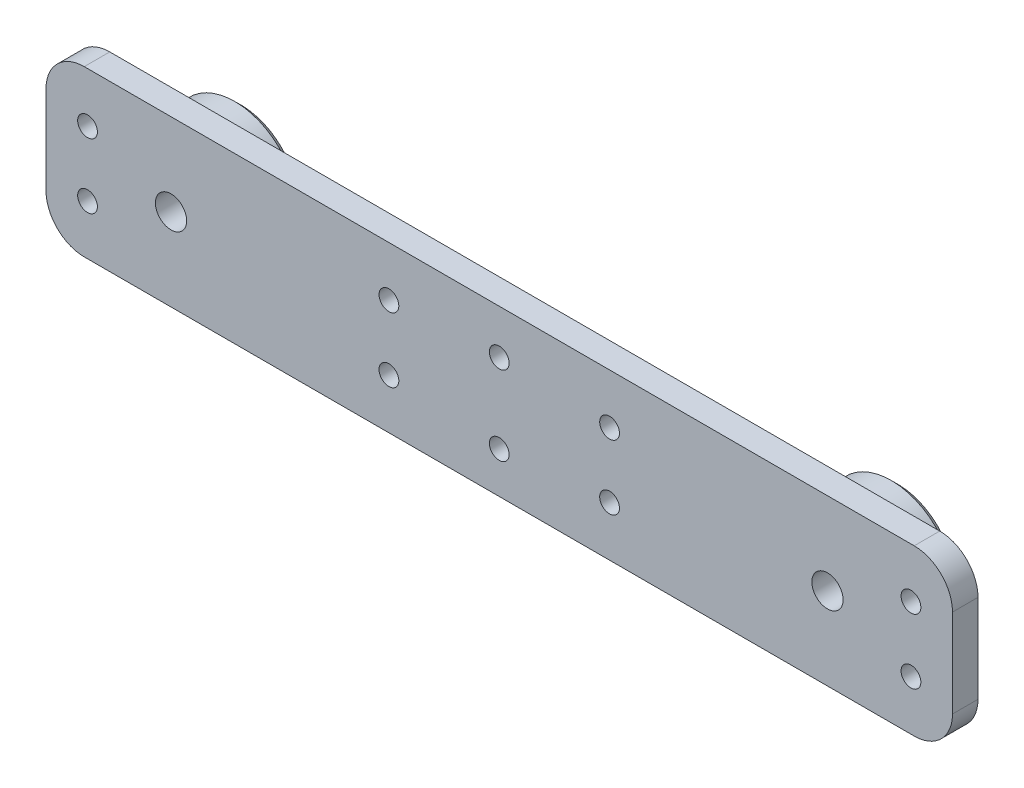
SolidWorks part; units mm, degrees
material "PET"
ref_plane "Front Plane" through (0, 0, 0) normal (0, 0, 1) x (1, 0, 0)
ref_plane "Top Plane" through (0, 0, 0) normal (0, 1, 0) x (1, 0, 0)
ref_plane "Right Plane" through (0, 0, 0) normal (1, 0, 0) x (0, 0, -1)
ref_plane "Plane1" through (0, 0, -8.279) normal (0, 0, -1) x (-1, 0, 0)
sketch "Sketch1" plane through (0, 0, -8.279) normal (0, 0, -1) x (-1, 0, 0)
  line L0 (-112, 9.158) -> (30.1427, 9.158)
  line L1 (30.1427, 9.158) -> (30.1427, 35)
  line L2 (30.1427, 35) -> (-112, 35)
  line L3 (-112, 35) -> (-112, 9.158)
extrude "Boss-Extrude1" add sketch "Sketch1" against normal blind 4
ref_plane "Plane2" through (0, 22.079, 0) normal (0, 1, 0) x (1, 0, 0)
sketch "Sketch2" plane through (0, 22.079, 0) normal (0, 1, 0) x (1, 0, 0)
  line L0 (-0.54, 15.279) -> (-10.54, 15.279)
  line L1 (-10.54, 15.279) -> (-10.54, 8.279)
  line L2 (-10.54, 8.279) -> (-0.54, 8.279)
  line L3 (-0.54, 8.279) -> (-0.54, 15.279)
  line L4 (-10.54, 15.279) -> (-10.54, 8.279) construction
revolve "Revolve1" add sketch "Sketch2" angle 360 about L4 reverse direction yes
sketch "Sketch3" plane through (0, 22.079, 0) normal (0, 1, 0) x (1, 0, 0)
  line L0 (102.397, 15.279) -> (92.397, 15.279)
  line L1 (92.397, 15.279) -> (92.397, 8.279)
  line L2 (92.397, 8.279) -> (102.397, 8.279)
  line L3 (102.397, 8.279) -> (102.397, 15.279)
  line L4 (92.397, 15.279) -> (92.397, 8.279) construction
revolve "Revolve2" add sketch "Sketch3" angle 360 about L4 reverse direction yes
hole_wizard "Ø3.1 (3.1) Diameter Hole1" positions "Sketch5" profile "Sketch4" hole size "Ø3.1" standard "ANSI Metric"
sketch "Sketch5" plane through (0, 0, -4.279) normal (0, 0, 1) x (1, 0, 0)
  point P0 (40.9286, 28.0395)
  point P1 (40.9286, 15.6185)
  point P2 (58.2273, 27.164)
  point P3 (23.63, 27.164)
  point P4 (-23.63, 27.164)
  point P5 (-23.63, 16.994)
  point P6 (23.63, 16.994)
  point P7 (58.2273, 16.994)
  point P8 (105.4873, 27.164)
  point P9 (105.4873, 16.994)
sketch "Sketch4" plane through (40.9286, 28.0395, -4.279) normal (1, 0, 0) x (0, -1, 0)
  line L0 (0, 0) -> (0, 11)
  line L1 (0, 11) -> (1.55, 11)
  line L2 (1.55, 11) -> (1.55, 0)
  line L5 (1.55, 0) -> (0, 0)
  line L11 (0, -6.35) -> (0, 107.95) construction
  dimension "Thru Hole Dia." = 3.1
  dimension "Thru Hole Depth" = 11
hole_wizard "Ø6.0 (6) Diameter Hole1" positions "Sketch7" profile "Sketch6" hole size "Ø6.0" standard "ANSI Metric"
sketch "Sketch7" plane through (0, 0, -15.279) normal (0, 0, -1) x (-1, 0, 0)
  point P0 (-92.397, 22.0793)
  point P1 (10.54, 22.079)
sketch "Sketch6" plane through (92.397, 22.0793, -15.279) normal (1, 0, 0) x (0, 1, 0)
  line L0 (0, 0) -> (0, 11)
  line L1 (0, 11) -> (3, 11)
  line L2 (3, 11) -> (3, 0)
  line L5 (3, 0) -> (0, 0)
  line L11 (0, -6.35) -> (0, 107.95) construction
  dimension "Thru Hole Dia." = 6
  dimension "Thru Hole Depth" = 11
chamfer "Chamfer1" distance 1 angle 45 4 edges at (92.397, 32.079, -8.279) (-10.54, 32.079, -8.279) (102.397, 22.079, -15.279) (-0.54, 22.079, -15.279)
fillet "Fillet1" radius 6 4 edges at (-30.1427, 35, -6.279) (112, 35, -6.279) (-30.1427, 9.158, -6.279) (112, 9.158, -6.279) tangent propagation no
sketch "Sketch8" plane through (0, 0, -15.279) normal (0, 0, -1) x (-1, 0, 0)
  circle A0 centre (-92.397, 22.0793) radius 2.45
  circle A1 centre (10.54, 22.079) radius 2.45
  circle A2 centre (10.54, 22.079) radius 3
  circle A3 centre (-92.397, 22.0793) radius 3
  dimension "D1" = 4.9
extrude "Boss-Extrude3" add sketch "Sketch8" against normal up to surface (11 mm away) up to face at (89.397, 22.0793, -4.279)
